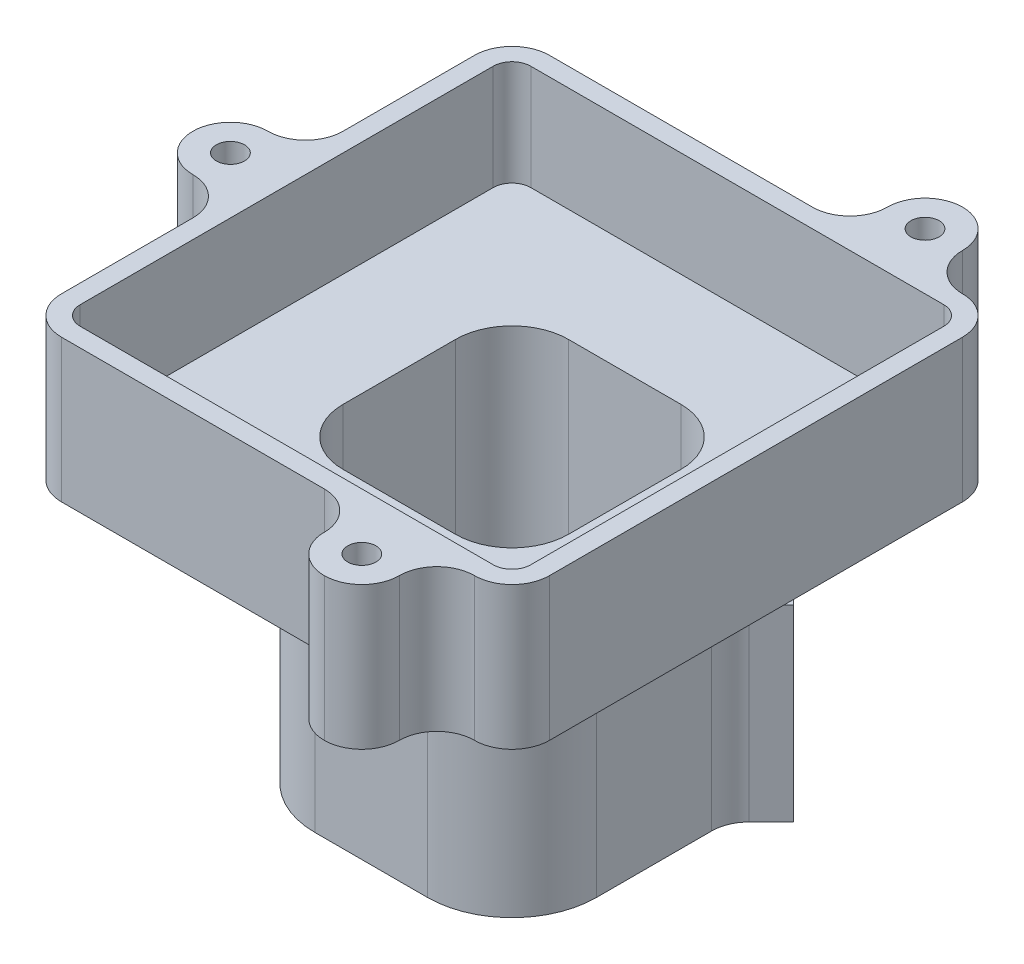
SolidWorks part; units mm, degrees
ref_plane "Front Plane" through (0, 0, 0) normal (0, 0, 1) x (1, 0, 0)
ref_plane "Top Plane" through (0, 0, 0) normal (0, 1, 0) x (1, 0, 0)
ref_plane "Right Plane" through (0, 0, 0) normal (1, 0, 0) x (0, 0, -1)
sketch "Sketch1" plane through (0, 0, 0) normal (0, 1, 0) x (1, 0, 0)
  line L1 (-3.75, 3.75) -> (3.75, 3.75)
  line L2 (-3.75, 3.75) -> (-3.75, -3.75)
  line L3 (-3.75, -3.75) -> (3.75, -3.75)
  line L4 (3.75, 3.75) -> (3.75, -3.75)
  line L5 (-3.75, 3.75) -> (3.75, -3.75) construction
  line L6 (-3.75, -3.75) -> (3.75, 3.75) construction
  dimension "D2" = 7.5
extrude "Boss-Extrude1" add sketch "Sketch1" along normal blind 7
sketch "Sketch2" plane through (0, 7, 0) normal (0, 1, 0) x (1, 0, 0)
  line L1 (6.5, 6.5) -> (-6.5, 6.5)
  line L2 (6.5, 6.5) -> (6.5, -6.5)
  line L3 (6.5, -6.5) -> (-6.5, -6.5)
  line L4 (-6.5, 6.5) -> (-6.5, -6.5)
  line L5 (6.5, 6.5) -> (-6.5, -6.5) construction
  line L6 (6.5, -6.5) -> (-6.5, 6.5) construction
  point P0 (0, 0)
  dimension "D1" = 13
  dimension "D2" = 13
extrude "Boss-Extrude2" add sketch "Sketch2" along normal blind 3.8
sketch "Sketch3" plane through (0, 0, 0) normal (0, -1, 0) x (1, 0, 0)
  line L1 (-3, -3) -> (3, -3)
  line L2 (-3, -3) -> (-3, 3)
  line L3 (-3, 3) -> (3, 3)
  line L4 (3, -3) -> (3, 3)
  line L5 (-3, -3) -> (3, 3) construction
  line L6 (-3, 3) -> (3, -3) construction
  dimension "D2" = 6
extrude "Cut-Extrude1" cut sketch "Sketch3" against normal through all
sketch "Sketch6" plane through (0, 10.8, 0) normal (0, 1, 0) x (1, 0, 0)
  line L1 (6, 6) -> (-6, 6)
  line L2 (6, 6) -> (6, -6)
  line L3 (6, -6) -> (-6, -6)
  line L4 (-6, 6) -> (-6, -6)
  line L5 (6, 6) -> (-6, -6) construction
  line L6 (6, -6) -> (-6, 6) construction
  point P0 (0, 0)
  dimension "D1" = 12
  dimension "D2" = 12
extrude "Cut-Extrude3" cut sketch "Sketch6" against normal offset from surface (2.8 mm away) 1 up to face at (0, 7, 0)
fillet "Fillet1" radius 0.5 4 edges at (-6, 9.4, -6) (6, 9.4, -6) (6, 9.4, 6) (-6, 9.4, 6)
sketch "Sketch12" plane through (0, 0, 0) normal (0, -1, 0) x (1, 0, 0)
  line L0 (4.6339, -2.8661) -> (3.75, -1.9822)
  line L1 (3.75, 3.75) -> (3.75, -3.75) construction
  line L2 (3.75, -1.9822) -> (1.9822, -3.75)
  line L3 (3.75, -3.75) -> (-3.75, -3.75) construction
  line L4 (1.9822, -3.75) -> (2.8661, -4.6339)
  line L5 (2.8661, -4.6339) -> (4.6339, -2.8661)
  dimension "D1" = 45
  dimension "D2" = 2.5
extrude "Boss-Extrude3" add sketch "Sketch12" against normal up to next
fillet "Fillet4" radius 1.5 4 edges at (-3, 4, -3) (-3, 4, 3) (3, 4, 3) (3, 4, -3)
fillet "Fillet2" radius 1 2 edges at (3.75, 3.5, -1.9822) (1.9822, 3.5, -3.75)
sketch "Sketch13" plane through (3.75, 0, -3.75) normal (0.7071, 0, -0.7071) x (-0.7071, 0, -0.7071)
  line L0 (0, 0) -> (0, 1.25) construction
  line L1 (1.25, 0) -> (-1.25, 0) construction
  line L2 (0, 1.25) -> (0, 3.75) construction
  dimension "D1" = 1.25
  dimension "D2" = 2.5
hole_wizard "Tap Drill for #0-80 Tap1" positions "Sketch15" profile "Sketch14" hole size "#0-80" standard "ANSI Inch"
sketch "Sketch15" plane through (3.75, 0, -3.75) normal (0.7071, 0, -0.7071) x (-0.7071, 0, -0.7071)
  point P0 (0, 1.25)
  point P3 (0, 3.75)
sketch "Sketch14" plane through (3.75, 1.25, -3.75) normal (0, 1, 0) x (-0.7071, 0, -0.7071)
  line L0 (0, 0) -> (0, 7.4679)
  line L1 (0, 7.4679) -> (0.5956, 7.11)
  line L2 (0.5956, 7.11) -> (0.5956, 0)
  line L5 (0.5956, 0) -> (0, 0)
  line L10 (0, 7.4679) -> (-0.5956, 7.11) construction
  line L11 (0, -6.35) -> (0, 107.95) construction
  dimension "Hole Dia." = 1.1913
  dimension "Hole Depth" = 7.11
  dimension "Drill Angle" = 118
fillet "Fillet5" radius 2.25 3 edges at (3.75, 3.5, 3.75) (-3.75, 3.5, 3.75) (-3.75, 3.5, -3.75)
sketch "Sketch16" plane through (3.75, 0, -3.75) normal (0.7071, 0, -0.7071) x (-0.7071, 0, -0.7071)
  line L0 (-1.25, 7) -> (-1.25, 0) construction
  line L1 (1.25, 7) -> (-1.25, 7)
  line L2 (1.25, 7) -> (1.25, 5)
  line L3 (1.25, 5) -> (-1.25, 5)
  line L4 (-1.25, 7) -> (-1.25, 5)
  line L6 (1.25, 0) -> (-1.25, 0) construction
  dimension "D1" = 5
extrude "Cut-Extrude4" cut sketch "Sketch16" against normal up to vertex (0.8358 mm away)
fillet "Fillet6" radius 1 4 edges at (-6.5, 8.9, 6.5) (-6.5, 8.9, -6.5) (6.5, 8.9, 6.5) (6.5, 8.9, -6.5)
sketch "Sketch17" plane through (0, 10.8, 0) normal (0, 1, 0) x (1, 0, 0)
  line L0 (-6.5, 5.5) -> (-6.5, -5.5) construction
  line L1 (-5.5, -6.5) -> (5.5, -6.5) construction
  line L2 (0, 0) -> (-7.5, 0) construction
  line L3 (-8.5, 1) -> (-6.5, 1)
  line L4 (-8.5, 1) -> (-8.5, -1)
  line L5 (-8.5, -1) -> (-6.5, -1)
  line L6 (-6.5, 1) -> (-6.5, -1)
  line L7 (-8.5, 1) -> (-6.5, -1) construction
  line L8 (-8.5, -1) -> (-6.5, 1) construction
  line L9 (4.5, -8.5) -> (2.5, -8.5)
  line L10 (4.5, -8.5) -> (4.5, -6.5)
  line L11 (4.5, -6.5) -> (2.5, -6.5)
  line L12 (2.5, -8.5) -> (2.5, -6.5)
  line L13 (4.5, -8.5) -> (2.5, -6.5) construction
  line L14 (4.5, -6.5) -> (2.5, -8.5) construction
  line L15 (4.5, 6.5) -> (2.5, 8.5) construction
  line L16 (4.5, 8.5) -> (2.5, 6.5) construction
  line L17 (2.5, 8.5) -> (2.5, 6.5)
  line L18 (4.5, 6.5) -> (2.5, 6.5)
  line L19 (4.5, 8.5) -> (4.5, 6.5)
  line L20 (4.5, 8.5) -> (2.5, 8.5)
  circle A0 centre (-7.5, 0) radius 0.375
  circle A1 centre (3.5, -7.5) radius 0.375
  circle A2 centre (3.5, 7.5) radius 0.375
  point P0 (-7.5, 0)
  point P11 (3.5, -7.5)
  point P22 (3.5, 7.5)
  dimension "D2" = 0.75
  dimension "D1" = 2
  dimension "D3" = 2
  dimension "D4" = 1
extrude "Boss-Extrude4" add sketch "Sketch17" against normal up to surface (3.8 mm away) up to face at (0.5879, 7, -0.5879)
fillet "Fillet7" radius 1 12 edges at (-6.5, 8.9, 1) (-8.5, 8.9, 1) (-8.5, 8.9, -1) (-6.5, 8.9, -1) (2.5, 8.9, -6.5) (2.5, 8.9, -8.5) (4.5, 8.9, -8.5) (4.5, 8.9, -6.5) (2.5, 8.9, 6.5) (2.5, 8.9, 8.5) (4.5, 8.9, 8.5) (4.5, 8.9, 6.5)
